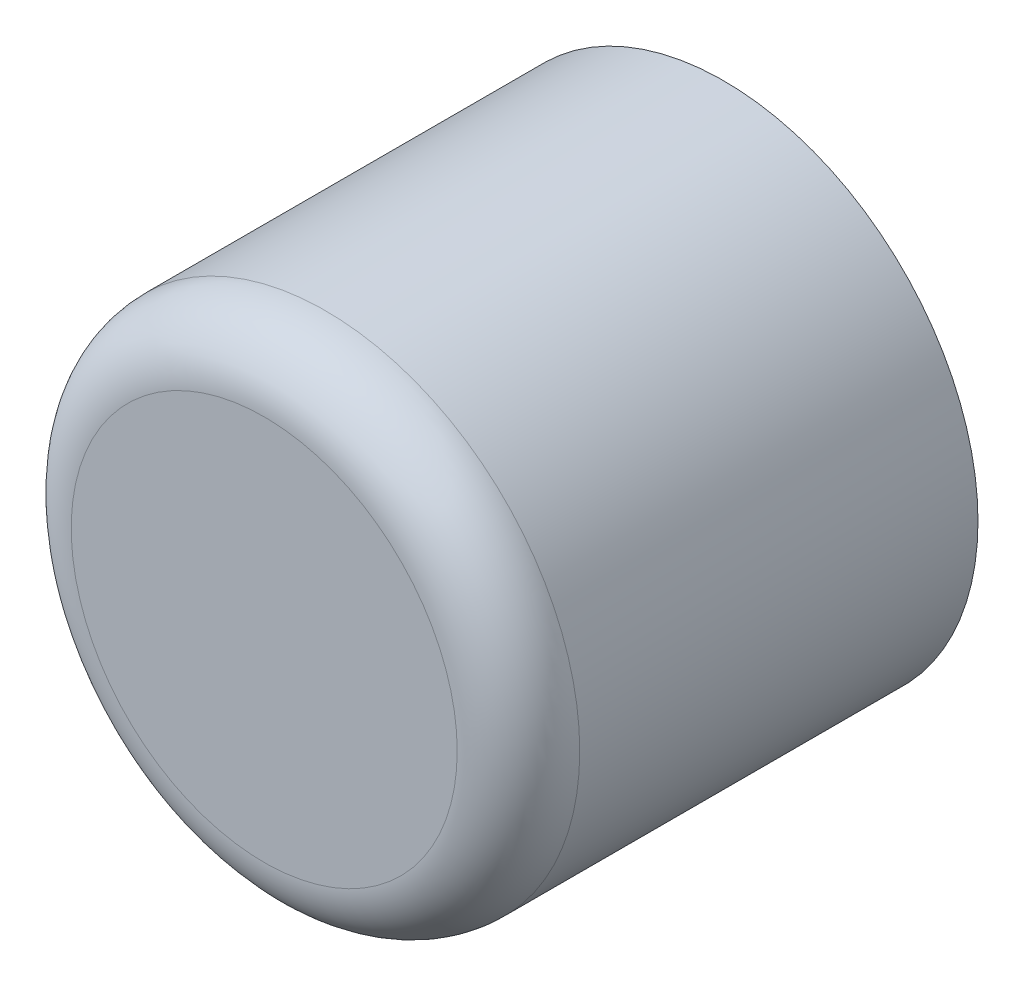
SolidWorks part; units mm, degrees
ref_plane "Front Plane" through (0, 0, 0) normal (0, 0, 1) x (1, 0, 0)
ref_plane "Top Plane" through (0, 0, 0) normal (0, 1, 0) x (1, 0, 0)
ref_plane "Right Plane" through (0, 0, 0) normal (1, 0, 0) x (0, 0, -1)
sketch "Sketch1" plane through (0, 0, 0) normal (0, 0, 1) x (1, 0, 0)
  circle A2 centre (-7.4682, 21.7741) radius 8.3
  circle A3 centre (-7.4682, 21.7741) radius 8.3
  dimension "D1" = 1.8
extrude "Boss-Extrude1" add sketch "Sketch1" along normal blind 15
move or copy body "Body-Move/Copy1" bodies to move or copy 101 copy no translate (0, 0, 10.7303)
shell "Shell1" thickness 1.8 removed face at (0.8318, 21.7741, 10.7303)
move or copy body "Body-Move/Copy2" bodies to move or copy 102 copy no translate (0, 0, -89.2287)
move or copy body "Body-Move/Copy3" bodies to move or copy 103 copy no translate (0, 0, 71.4709)
move or copy body "Body-Move/Copy4" bodies to move or copy 104 copy no translate (0, 0, -97.1728)
move or copy body "Body-Move/Copy5" bodies to move or copy 105 copy no translate (0, 0, 30.228)
fillet "Fillet1" radius 2 1 edges at (0.8318, 21.7741, -58.9722)
sketch "Sketch2" plane through (0, 0, -73.9722) normal (0, 0, -1) x (-1, 0, 0)
  circle A2 centre (7.4682, 21.7741) radius 6.7
  circle A3 centre (7.4682, 21.7741) radius 6.7
  dimension "D1" = 0.2
extrude "Cut-Extrude1" cut sketch "Sketch2" against normal blind 12
thread "Thread1" pitch 2.1167 method cut profile "Thread Profile1" start angle 0, offset 1, length 10, pitch 2.1167, diameter 13.4
ref_plane "Plane1" through (-0.7682, 21.7741, -74.9722) normal (0, -1, 0) x (1, 0, 0)
sketch "Thread Profile1" plane through (-0.7682, 21.7741, -74.9722) normal (0, -1, 0) x (1, 0, 0)
  line L0 (0, 0) -> (0, 2.1167) construction
  line L1 (0, 0) -> (1.1457, 0.6615)
  line L2 (1.1457, 0.6615) -> (1.1457, 0.926)
  line L3 (1.1457, 0.926) -> (0, 1.5875)
  line L4 (1.1457, 0.7937) -> (0, 0.7937) construction
  line L11 (0, 0) -> (0, 1.5875)
  point P2 (0, 0)
  dimension "Pitch" = 2.1167
  dimension "Profile_Angle" = 60
  dimension "Profile_Land" = 0.2646
  dimension "Profile_Height" = 1.1457
